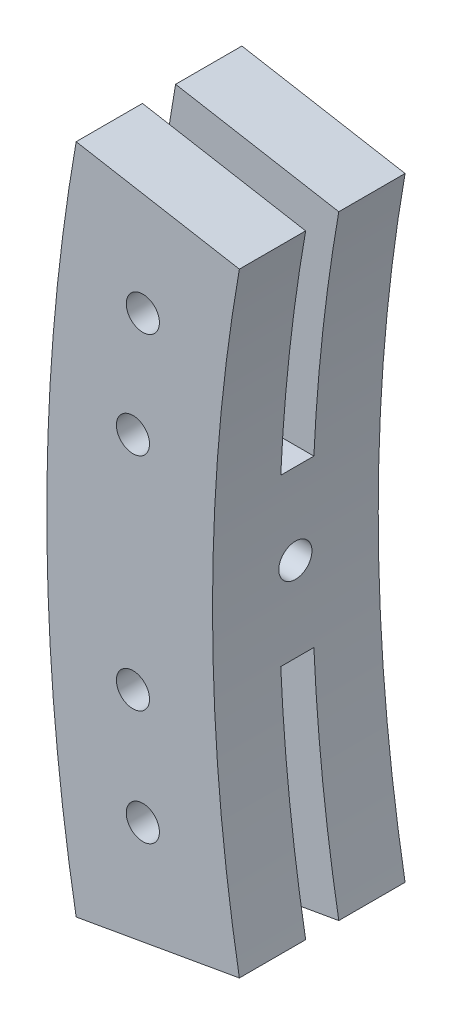
SolidWorks part; units mm, degrees
ref_plane "Front Plane" through (0, 0, 0) normal (0, 0, 1) x (1, 0, 0)
ref_plane "Top Plane" through (0, 0, 0) normal (0, 1, 0) x (1, 0, 0)
ref_plane "Right Plane" through (0, 0, 0) normal (1, 0, 0) x (0, 0, -1)
sketch "Sketch1" plane through (0, 0, 0) normal (0, 0, 1) x (1, 0, 0)
  line L0 (160, 0) -> (-167.5, 0) construction
  line L1 (0, 160) -> (0, -160) construction
  line L2 (0, 0) -> (-157.5692, 27.7837) construction
  line L3 (0, 0) -> (-157.5692, -27.7837) construction
  line L4 (-157.5692, 27.7837) -> (-172.3414, 30.3884)
  line L5 (-157.5692, -27.7837) -> (-172.3414, -30.3884)
  arc A0 (-157.5692, 27.7837) -> (-157.5692, -27.7837) centre (0, 0) ccw
  arc A1 (-172.3414, 30.3884) -> (-172.3414, -30.3884) centre (0, 0) ccw
  circle A2 centre (0, 0) radius 167.5 construction
  dimension "D1" = 320
  dimension "D2" = 350
  dimension "D4" = 7.5
  dimension "D3" = 20
extrude "Boss-Extrude3" add sketch "Sketch1" along normal mid plane 15 contours L4 A1 A0 | A1 L5 A0 | A1 A0 region at (-166.7623, 0, 0)
extrude "Cut-Extrude4" cut sketch "Sketch1<6>" against normal mid plane 3
sketch "Sketch1<6>" plane through (0, 0, 0) normal (0, 0, 1) x (1, 0, 0) same geometry as "Sketch1"
sketch "Sketch6" plane through (0, 0, 0) normal (0, 0, 1) x (1, 0, 0)
  line L1 (-184.1488, 7.5) -> (-150.8512, 7.5)
  line L2 (-184.1488, 7.5) -> (-184.1488, -7.5)
  line L3 (-184.1488, -7.5) -> (-150.8512, -7.5)
  line L4 (-150.8512, 7.5) -> (-150.8512, -7.5)
  line L5 (-184.1488, 7.5) -> (-150.8512, -7.5) construction
  line L6 (-184.1488, -7.5) -> (-150.8512, 7.5) construction
  arc A0 (-172.3414, 30.3884) -> (-172.3414, -30.3884) centre (0, 0) ccw construction
  arc A1 (-157.5692, 27.7837) -> (-157.5692, -27.7837) centre (0, 0) ccw construction
  arc A2 (-172.3414, 30.3884) -> (-172.3414, -30.3884) centre (0, 0) ccw
  arc A3 (-157.5692, 27.7837) -> (-157.5692, -27.7837) centre (0, 0) ccw
  point P0 (-167.5, 0)
  dimension "D1" = 15
extrude "Boss-Extrude5" add sketch "Sketch6" along normal mid plane 3 contours A3 L1 A2 L3 region at (-167.4439, 0, 0)
ref_plane "Plane1" through (-167.5, 0, 0) normal (1, 0, 0) x (0, 0, -1)
sketch "Sketch4" plane through (-167.5, 0, 0) normal (1, 0, 0) x (0, 0, -1)
  circle A0 centre (0, 0) radius 3
  dimension "D1" = 6
extrude "bearing hole" cut sketch "Sketch4" against normal mid plane 2.5
sketch "Sketch7" plane through (-167.5, 0, 0) normal (1, 0, 0) x (0, 0, -1)
  circle A0 centre (0, 0) radius 1.5
  dimension "D1" = 3
extrude "shaft hole" cut sketch "Sketch7" against normal blind 2.5 and the other way through all
sketch "Sketch8" plane through (0, 0, 0) normal (0, 0, 1) x (1, 0, 0)
  line L0 (-160, 0) -> (-175, 0)
  line L2 (-157.5692, 27.7837) -> (-172.3414, 30.3884)
  line L3 (-172.3414, -30.3884) -> (-157.5692, -27.7837)
  line L4 (-157.5692, 27.7837) -> (-172.3414, 30.3884) construction
  line L5 (-172.3414, -30.3884) -> (-157.5692, -27.7837) construction
  arc A0 (-164.9553, 29.0861) -> (-164.9553, -29.0861) centre (0, 0) ccw construction
  arc A1 (-172.3414, 30.3884) -> (-172.3414, -30.3884) centre (0, 0) ccw construction
  circle A2 centre (-166.3065, 19.9599) radius 1.5
  circle A3 centre (-167.2012, 10) radius 1.5
  arc A4 (-157.5692, 27.7837) -> (-157.5692, -27.7837) centre (0, 0) ccw
  arc A5 (-172.3414, 30.3884) -> (-172.3414, -30.3884) centre (0, 0) ccw
  arc A6 (-157.5692, 27.7837) -> (-157.5692, -27.7837) centre (0, 0) ccw construction
  arc A7 (-172.3414, 30.3884) -> (-172.3414, -30.3884) centre (0, 0) ccw construction
  circle A8 centre (-167.2012, -10) radius 1.5
  circle A9 centre (-166.3065, -19.9599) radius 1.5
  point P19 (0, 0)
  point P24 (-172.3414, -30.3884)
  dimension "D1" = 7.5
  dimension "D3" = 3
  dimension "D4" = 10
  dimension "D5" = 10
  dimension "D2" = 0
extrude "Cut-Extrude6" cut sketch "Sketch8" against normal through all both and the other way through all contours A2 | A3 | A8 | A9
